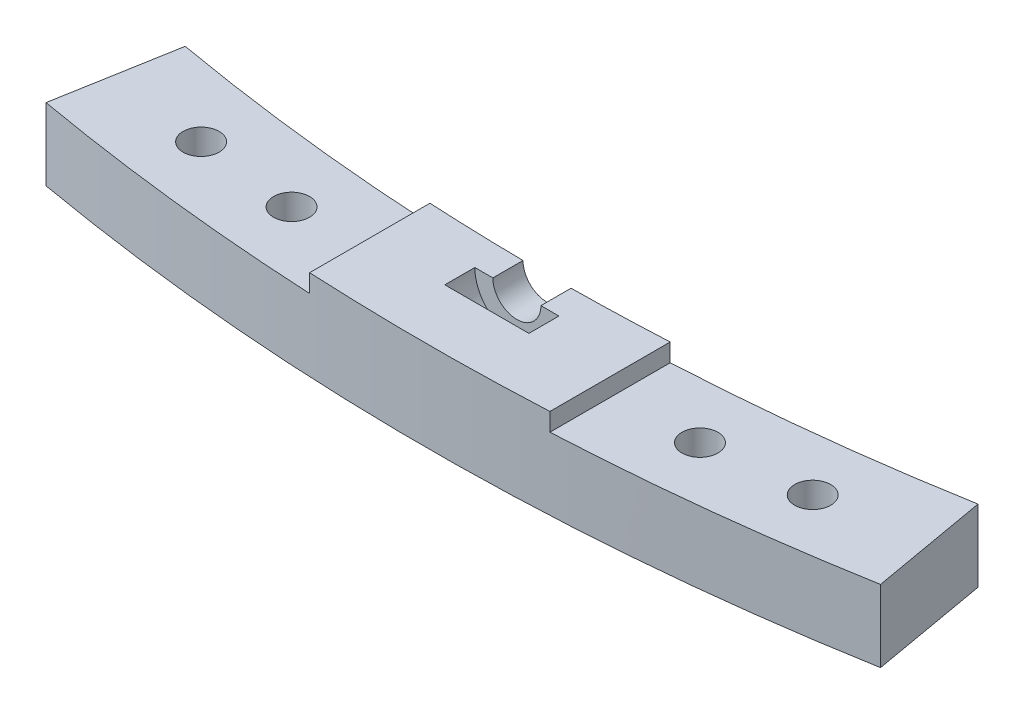
SolidWorks part; units mm, degrees
ref_plane "Front Plane" through (0, 0, 0) normal (0, 0, 1) x (1, 0, 0)
ref_plane "Top Plane" through (0, 0, 0) normal (0, 1, 0) x (1, 0, 0)
ref_plane "Right Plane" through (0, 0, 0) normal (1, 0, 0) x (0, 0, -1)
ref_plane "Plane1" through (0, -7.5, 0) normal (0, 1, 0) x (1, 0, 0)
sketch "Sketch2" plane through (0, -7.5, 0) normal (0, 1, 0) x (1, 0, 0)
  line L0 (0, 200) -> (0, -200) construction
  line L1 (0, 200) -> (0, -200) construction
  line L2 (0, 0) -> (-34.7296, -196.9616) construction
  line L3 (0, 0) -> (34.7296, -196.9616) construction
  line L4 (-32.9932, -187.1135) -> (-34.7296, -196.9616)
  line L5 (32.9932, -187.1135) -> (34.7296, -196.9616)
  line L6 (10, -199.7498) -> (10, -189.7367) construction
  line L7 (-10, -199.7498) -> (-10, -189.7367) construction
  line L8 (10, -199.7498) -> (10, -189.7367)
  line L9 (-10, -199.7498) -> (-10, -189.7367)
  circle A0 centre (0, 0) radius 195 construction
  circle A1 centre (0, 0) radius 195 construction
  arc A2 (-199.7498, -10) -> (-10, -199.7498) centre (0, 0) ccw construction
  arc A3 (10, -199.7498) -> (199.7498, -10) centre (0, 0) ccw construction
  arc A4 (-34.7296, -196.9616) -> (34.7296, -196.9616) centre (0, 0) ccw
  arc A5 (-32.9932, -187.1135) -> (32.9932, -187.1135) centre (0, 0) ccw
  arc A6 (-189.7367, -10) -> (-10, -189.7367) centre (0, 0) ccw construction
  dimension "D1" = 20
extrude "Boss-Extrude3" add sketch "Sketch2" along normal up to surface (6 mm away) contours A5 L4 A4 L9 | A5 L8 A4 L5 region at (-21.9638, -7.5, 193.6958) region at (21.9638, -7.5, 193.6958)
extrude "Boss-Extrude4" add sketch "Sketch2<3>" along normal up to surface (7.5 mm away) contours A5 L9 A4 L8 region at (0, -7.5, 194.9144)
sketch "Sketch2<3>" plane through (0, -7.5, 0) normal (0, 1, 0) x (1, 0, 0) same geometry as "Sketch2"
sketch "Sketch3" plane through (0, 0, 0) normal (0, 1, 0) x (1, 0, 0)
  line L0 (0, 0) -> (0, -195) construction
  line L1 (-2, -195) -> (2, -195) construction
  line L2 (2, -195) -> (2, -175) construction
  line L3 (3.5, -192.5) -> (2, -192.5)
  line L4 (3.5, -192.5) -> (3.5, -195)
  line L5 (3.5, -195) -> (0, -195)
  line L9 (2, -180) -> (0, -180)
  line L10 (2, -180) -> (2, -192.5)
  line L15 (0, -195) -> (0, -180)
  dimension "D1" = 2.5
  dimension "D2" = 7
revolve "hole" cut sketch "Sketch3" angle 360 about L0
sketch "Sketch4" plane through (0, -7.5, 0) normal (0, -1, 0) x (1, 0, 0)
  circle A0 centre (25.4526, 193.3317) radius 1.5 construction
  circle A1 centre (16.9954, 194.258) radius 1.5 construction
  circle A2 centre (-25.4526, 193.3317) radius 1.5 construction
  circle A3 centre (-16.9954, 194.258) radius 1.5 construction
  circle A4 centre (25.4526, 193.3317) radius 1.5
  circle A5 centre (16.9954, 194.258) radius 1.5
  circle A6 centre (-25.4526, 193.3317) radius 1.5
  circle A7 centre (-16.9954, 194.258) radius 1.5
extrude "Cut-Extrude1" cut sketch "Sketch4" against normal through all both and the other way through all
